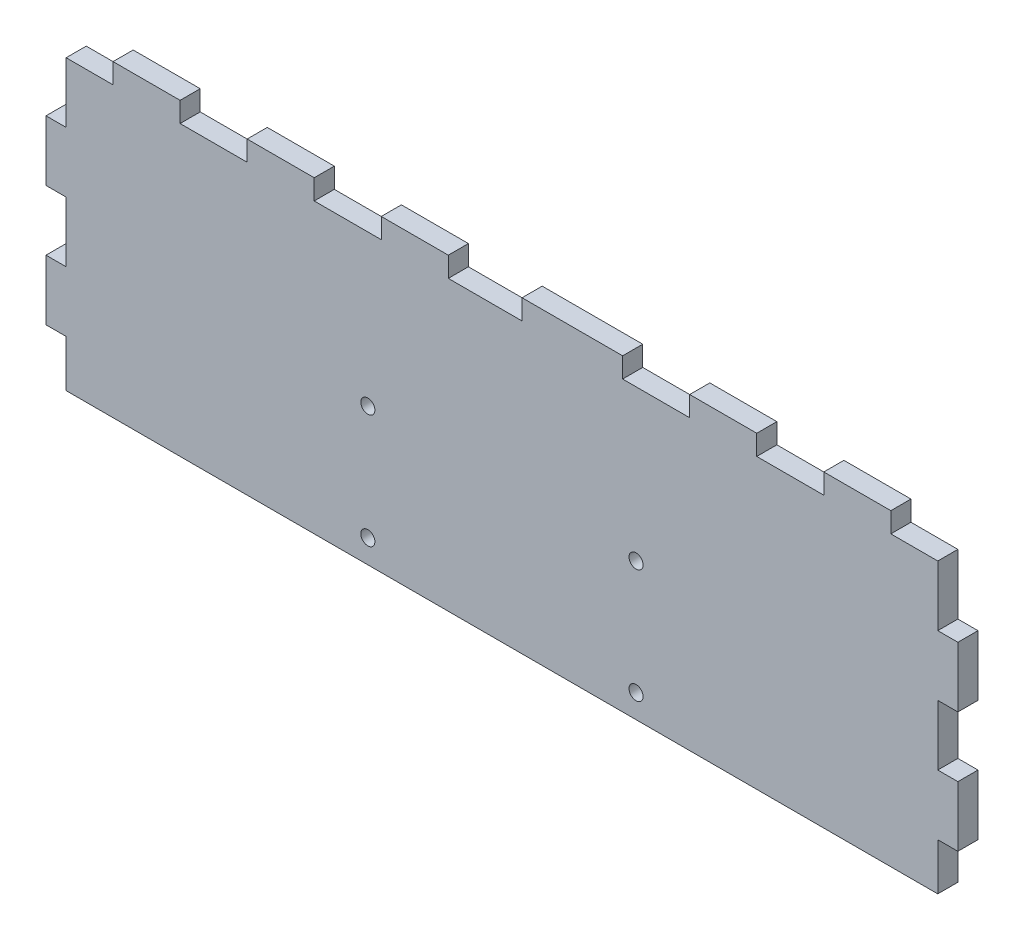
SolidWorks part; units mm, degrees
ref_plane "Front Plane" through (0, 0, 0) normal (0, 0, 1) x (1, 0, 0)
ref_plane "Top Plane" through (0, 0, 0) normal (0, 1, 0) x (1, 0, 0)
ref_plane "Right Plane" through (0, 0, 0) normal (1, 0, 0) x (0, 0, -1)
sketch "Sketch1" plane through (0, 0, 0) normal (0, 0, 1) x (1, 0, 0)
  line L4 (0, 0) -> (136, 0)
  line L5 (136, 0) -> (136, 46)
  line L6 (136, 46) -> (0, 46)
  line L7 (0, 46) -> (0, 0)
  line L8 (0, 0) -> (136, 0)
  line L9 (136, 0) -> (136, 46)
  line L10 (136, 46) -> (0, 46)
  line L11 (0, 46) -> (0, 0)
  circle A0 centre (88, 20.5) radius 1.05 construction
  circle A1 centre (48, 20.5) radius 1.05 construction
  circle A2 centre (48, 3.5) radius 1.05 construction
  circle A3 centre (88, 3.5) radius 1.05 construction
  circle A4 centre (88, 20.5) radius 1.05
  circle A5 centre (48, 20.5) radius 1.05
  circle A6 centre (48, 3.5) radius 1.05
  circle A7 centre (88, 3.5) radius 1.05
  dimension "D1" = 0
extrude "Boss-Extrude1" add sketch "Sketch1" along normal blind 3
sketch "Sketch4" plane through (0, 0, 3) normal (0, 0, 1) x (1, 0, 0)
  line L0 (136, 0) -> (136, 7) construction
  line L1 (136, 7) -> (133, 7) construction
  line L2 (133, 7) -> (133, 0) construction
  line L3 (133, 0) -> (136, 0) construction
  line L4 (133, 25) -> (133, 16) construction
  line L5 (133, 16) -> (136, 16) construction
  line L6 (136, 16) -> (136, 25) construction
  line L7 (136, 25) -> (133, 25) construction
  line L8 (136, 34) -> (136, 43) construction
  line L9 (133, 34) -> (136, 34) construction
  line L10 (133, 43) -> (133, 34) construction
  line L11 (136, 43) -> (133, 43) construction
  line L12 (126, 43) -> (136, 43) construction
  line L13 (126, 46) -> (126, 43) construction
  line L14 (136, 46) -> (126, 46) construction
  line L15 (136, 43) -> (136, 46) construction
  line L16 (40, 43) -> (50, 43) construction
  line L17 (50, 43) -> (50, 46) construction
  line L18 (50, 46) -> (40, 46) construction
  line L19 (40, 46) -> (40, 43) construction
  line L20 (60, 43) -> (71, 43) construction
  line L21 (71, 43) -> (71, 46) construction
  line L22 (71, 46) -> (60, 46) construction
  line L23 (60, 46) -> (60, 43) construction
  line L24 (86, 43) -> (96, 43) construction
  line L25 (96, 43) -> (96, 46) construction
  line L26 (96, 46) -> (86, 46) construction
  line L27 (86, 46) -> (86, 43) construction
  line L28 (106, 46) -> (106, 43) construction
  line L29 (106, 43) -> (116, 43) construction
  line L30 (116, 43) -> (116, 46) construction
  line L31 (116, 46) -> (106, 46) construction
  line L32 (0, 25) -> (0, 16) construction
  line L33 (0, 16) -> (3, 16) construction
  line L34 (3, 16) -> (3, 25) construction
  line L35 (3, 25) -> (0, 25) construction
  line L36 (0, 43) -> (10, 43) construction
  line L37 (10, 43) -> (10, 46) construction
  line L38 (10, 46) -> (0, 46) construction
  line L39 (0, 46) -> (0, 43) construction
  line L40 (0, 43) -> (0, 34) construction
  line L41 (0, 34) -> (3, 34) construction
  line L42 (3, 34) -> (3, 43) construction
  line L43 (3, 43) -> (0, 43) construction
  line L44 (30, 43) -> (30, 46) construction
  line L45 (30, 46) -> (20, 46) construction
  line L46 (20, 46) -> (20, 43) construction
  line L47 (20, 43) -> (30, 43) construction
  line L48 (0, 7) -> (0, 0) construction
  line L49 (0, 0) -> (3, 0) construction
  line L50 (3, 0) -> (3, 7) construction
  line L51 (3, 7) -> (0, 7) construction
  line L52 (136, 0) -> (136, 7)
  line L53 (136, 7) -> (133, 7)
  line L54 (133, 7) -> (133, 0)
  line L55 (133, 0) -> (136, 0)
  line L56 (133, 25) -> (133, 16)
  line L57 (133, 16) -> (136, 16)
  line L58 (136, 16) -> (136, 25)
  line L59 (136, 25) -> (133, 25)
  line L60 (136, 34) -> (136, 43)
  line L61 (133, 34) -> (136, 34)
  line L62 (133, 43) -> (133, 34)
  line L63 (136, 43) -> (133, 43)
  line L64 (126, 43) -> (136, 43)
  line L65 (126, 46) -> (126, 43)
  line L66 (136, 46) -> (126, 46)
  line L67 (136, 43) -> (136, 46)
  line L68 (40, 43) -> (50, 43)
  line L69 (50, 43) -> (50, 46)
  line L70 (50, 46) -> (40, 46)
  line L71 (40, 46) -> (40, 43)
  line L72 (60, 43) -> (71, 43)
  line L73 (71, 43) -> (71, 46)
  line L74 (71, 46) -> (60, 46)
  line L75 (60, 46) -> (60, 43)
  line L76 (86, 43) -> (96, 43)
  line L77 (96, 43) -> (96, 46)
  line L78 (96, 46) -> (86, 46)
  line L79 (86, 46) -> (86, 43)
  line L80 (106, 46) -> (106, 43)
  line L81 (106, 43) -> (116, 43)
  line L82 (116, 43) -> (116, 46)
  line L83 (116, 46) -> (106, 46)
  line L84 (0, 25) -> (0, 16)
  line L85 (0, 16) -> (3, 16)
  line L86 (3, 16) -> (3, 25)
  line L87 (3, 25) -> (0, 25)
  line L88 (0, 43) -> (10, 43)
  line L89 (10, 43) -> (10, 46)
  line L90 (10, 46) -> (0, 46)
  line L91 (0, 46) -> (0, 43)
  line L92 (0, 43) -> (0, 34)
  line L93 (0, 34) -> (3, 34)
  line L94 (3, 34) -> (3, 43)
  line L95 (3, 43) -> (0, 43)
  line L96 (30, 43) -> (30, 46)
  line L97 (30, 46) -> (20, 46)
  line L98 (20, 46) -> (20, 43)
  line L99 (20, 43) -> (30, 43)
  line L100 (0, 7) -> (0, 0)
  line L101 (0, 0) -> (3, 0)
  line L102 (3, 0) -> (3, 7)
  line L103 (3, 7) -> (0, 7)
  line M3 (0, 46) -> (0, 0)
  line M4 (0, 0) -> (136, 0)
  line M5 (136, 0) -> (136, 46)
  line M6 (136, 46) -> (0, 46)
extrude "Cut-Extrude1" cut sketch "Sketch4" against normal up to next contours L88 L89 M6 M3 | L93 L94 L88 M3 | L86 L87 L85 M3 | L102 L103 M3 M4 | L98 L99 L96 M6 | L71 L68 L69 M6 | L75 L72 L73 M6 | L79 L76 L77 M6 | L81 L82 L80 M6 | L65 L64 L63 M6 M5 | L63 L62 L61 M5 | L59 L56 L57 M5 | L53 L54 M4 M5 region at (134.5, 3.5, 3) region at (134.5, 20.5, 3) region at (1.5, 3.5, 3) region at (134.5, 38.5, 3) region at (131, 44.5, 3) region at (1.5, 20.5, 3) region at (1.5, 38.5, 3) region at (111, 44.5, 3) region at (5, 44.5, 3) region at (91, 44.5, 3) region at (25, 44.5, 3) region at (65.5, 44.5, 3) region at (45, 44.5, 3)
